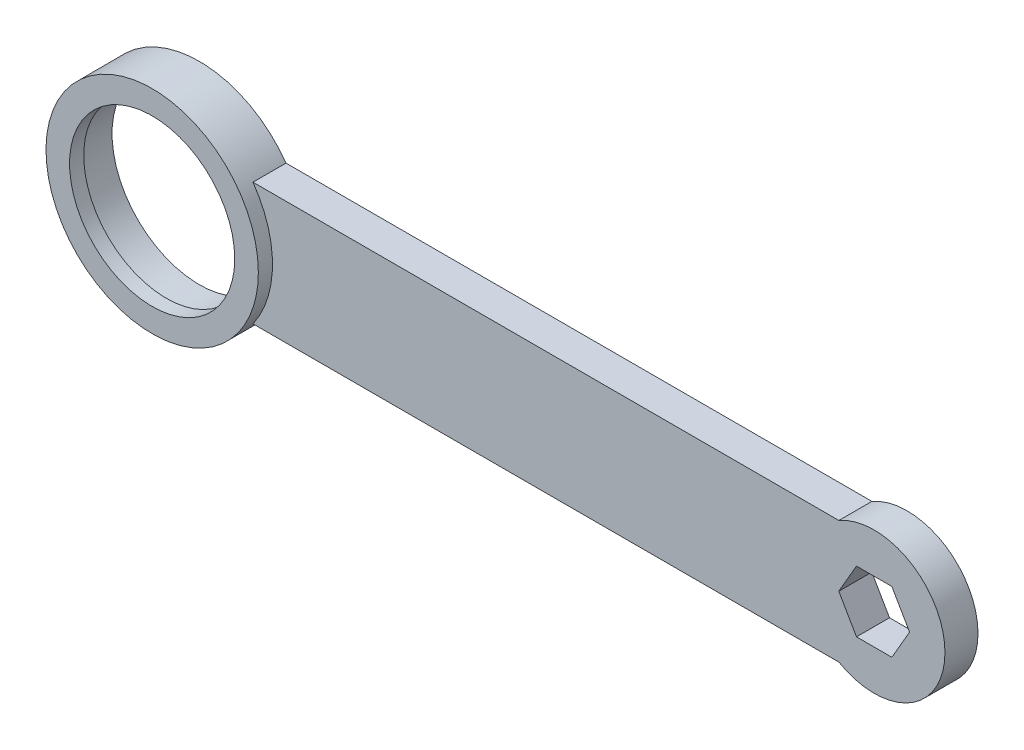
SolidWorks part; units mm, degrees
ref_plane "Front Plane" through (0, 0, 0) normal (0, 0, 1) x (1, 0, 0)
ref_plane "Top Plane" through (0, 0, 0) normal (0, 1, 0) x (1, 0, 0)
ref_plane "Right Plane" through (0, 0, 0) normal (1, 0, 0) x (0, 0, -1)
sketch "Sketch1" plane through (0, 0, 0) normal (0, 0, 1) x (1, 0, 0)
  line L0 (-75, 0) -> (75, 0) construction
  line L2 (-56.6356, 13) -> (67.5167, 13)
  line L3 (-56.6356, 13) -> (-56.6356, -13) construction
  line L4 (-56.6356, -13) -> (67.5167, -13)
  line L5 (67.5167, 13) -> (67.5167, -13) construction
  arc A0 (-56.6356, 13) -> (-56.6356, -13) centre (-75, 0) ccw
  arc A1 (67.5167, -13) -> (67.5167, 13) centre (75, 0) ccw
  point P4 (0, 0)
  point P10 (67.5167, 0)
  dimension "D2" = 45
  dimension "D3" = 30
  dimension "D1" = 150
  dimension "D4" = 26
extrude "Boss-Extrude1" add sketch "Sketch1" along normal blind 7
sketch "Sketch2" plane through (0, 0, 7) normal (0, 0, 1) x (1, 0, 0)
  circle A0 centre (-75, 0) radius 22.5
extrude "Boss-Extrude2" add sketch "Sketch2" along normal blind 3
sketch "Sketch3" plane through (0, 0, 7) normal (0, 0, 1) x (1, 0, 0)
  line L1 (82.5, 0) -> (78.75, 6.4952)
  line L2 (78.75, 6.4952) -> (71.25, 6.4952)
  line L3 (71.25, 6.4952) -> (67.5, 0)
  line L4 (67.5, 0) -> (71.25, -6.4952)
  line L5 (71.25, -6.4952) -> (78.75, -6.4952)
  line L6 (78.75, -6.4952) -> (82.5, 0)
  circle A0 centre (75, 0) radius 7.5 construction
  dimension "D1" = 15
extrude "Cut-Extrude1" cut sketch "Sketch3" against normal through all
sketch "Sketch4" plane through (0, 0, 10) normal (0, 0, 1) x (1, 0, 0)
  circle A0 centre (-75, 0) radius 17.5
  dimension "D1" = 35
extrude "Cut-Extrude2" cut sketch "Sketch4" against normal through all
sketch "Sketch5" plane through (0, 0, 0) normal (0, 0, 1) x (1, 0, 0)
  circle A0 centre (-75, 0) radius 18.5
  dimension "D1" = 37
extrude "Cut-Extrude3" cut sketch "Sketch5" along normal blind 7
